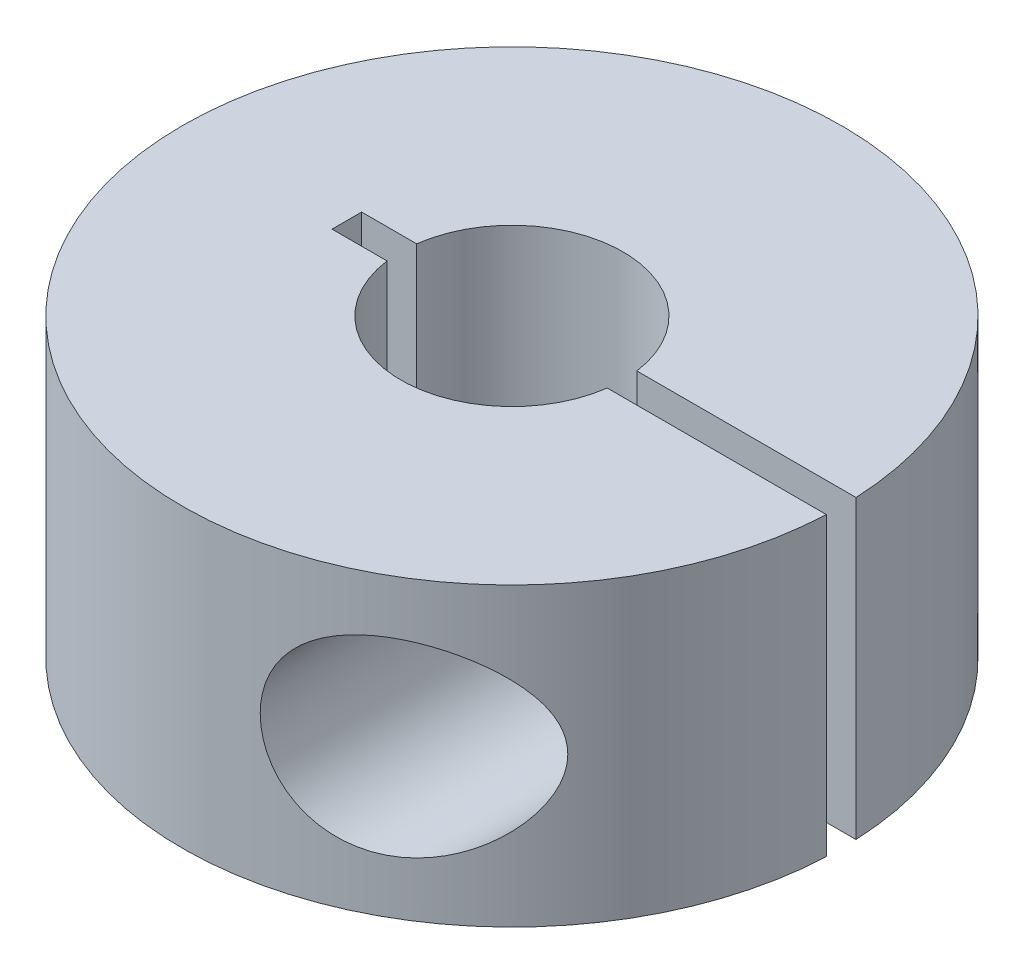
SolidWorks part; units mm, degrees
ref_plane "Front Plane" through (0, 0, 0) normal (0, 0, 1) x (1, 0, 0)
ref_plane "Top Plane" through (0, 0, 0) normal (0, 1, 0) x (1, 0, 0)
ref_plane "Right Plane" through (0, 0, 0) normal (1, 0, 0) x (0, 0, -1)
sketch "Sketch1" plane through (0, 0, 0) normal (0, 1, 0) x (1, 0, 0)
  circle A0 centre (0, 0) radius 11.125
  dimension "D1" = 22.25
extrude "Boss-Extrude1" add sketch "Sketch1" along normal blind 10
ref_plane "Plane1" through (0, 0, -3) normal (0, 0, 1) x (1, 0, 0)
sketch "Sketch2" plane through (0, 0, -3) normal (0, 0, 1) x (1, 0, 0)
  line L0 (0, 5) -> (11.125, 5) construction
  line L1 (11.125, 10) -> (-11.125, 10) construction
  line L2 (0, 0) -> (0, 10) construction
  line L3 (11.125, 0) -> (11.125, 10) construction
  line L5 (4.3581, 2.8954) -> (6.783, 2.9047)
  line L6 (6.783, 2.9047) -> (7.9874, 5.0093)
  line L7 (7.9874, 5.0093) -> (6.7669, 7.1046)
  line L8 (6.7669, 7.1046) -> (4.342, 7.0953)
  line L9 (4.342, 7.0953) -> (3.1376, 4.9907)
  line L10 (3.1376, 4.9907) -> (4.3581, 2.8954)
  circle A0 centre (5.5625, 5) radius 2.1 construction
  point P1 (0, 10)
  point P9 (5.5625, 5)
  dimension "D1" = 4.2
  dimension "D2" = 2.4249
extrude "Cut-Extrude1" cut sketch "Sketch2" against normal through all
sketch "Sketch3" plane through (0, 0, 0) normal (0, 1, 0) x (1, 0, 0)
  line L0 (-5.5735, 0.5) -> (-5.5735, -0.5)
  line L5 (-5.5735, -0.5) -> (11.4265, -0.5)
  line L6 (11.4265, -0.5) -> (11.4265, 0.5)
  line L12 (11.4265, 0.5) -> (-5.5735, 0.5)
  line L13 (-5.5735, 0) -> (11.4265, 0) construction
  point P3 (-0.5735, 0.5)
  point P7 (0, 0)
  dimension "D1" = 5
  dimension "D2" = 12
  dimension "D3" = 1
extrude "Cut-Extrude2" cut sketch "Sketch3" along normal through all
ref_plane "Plane2" through (0, 0, 4.6) normal (0, 0, 1) x (1, 0, 0)
sketch "Sketch6" plane through (0, 0, 4.6) normal (0, 0, 1) x (1, 0, 0)
  line L0 (0, 5) -> (11.125, 5) construction
  point P0 (5.5625, 5)
hole_wizard "CBORE for M2 Hex Head Machine Screw1" positions "Sketch6" profile "Sketch7" counterbore size "M2" standard "ANSI Metric" end condition through all
sketch "Sketch7" plane through (5.5625, 5, 4.6) normal (1, 0, 0) x (0, -1, 0)
  line L0 (0, 0) -> (0, 15.725)
  line L1 (0, 15.725) -> (1.2, 15.725)
  line L3 (1.2, 15.725) -> (1.2, 1.6)
  line L4 (1.2, 1.6) -> (3.19, 1.6)
  line L5 (3.19, 1.6) -> (3.19, 0)
  line L7 (3.19, 0) -> (0, 0)
  line L11 (0, -6.35) -> (0, 107.95) construction
  dimension "Thru Hole Dia." = 2.4
  dimension "Thru Hole Depth" = 15.725
  dimension "C'Bore Dia." = 6.38
  dimension "C'Bore Depth" = 1.6
sketch "Sketch8" plane through (0, 0, 4.6) normal (0, 0, 1) x (1, 0, 0)
  circle A0 centre (5.5625, 5) radius 3.19
  dimension "D1" = 6.38
extrude "Cut-Extrude3" cut sketch "Sketch8" along normal through all
sketch "Sketch9" plane through (0, 0, 0) normal (0, 1, 0) x (1, 0, 0)
  circle A0 centre (0, 0) radius 3.75
  dimension "AxleHoleDiameter" = 7.5
extrude "Cut-Extrude4" cut sketch "Sketch9" along normal through all both and the other way through all
sketch "Sketch10" plane through (0, 0, 0) normal (0, 0, 1) x (1, 0, 0)
  line L0 (0, 0) -> (0, 10) construction
  line L2 (3.7165, 10) -> (-3.7165, 10) construction
  point P3 (0, 10)
ref_axis "Axis1" through (0, 0, 0) along (0, 1, 0)
